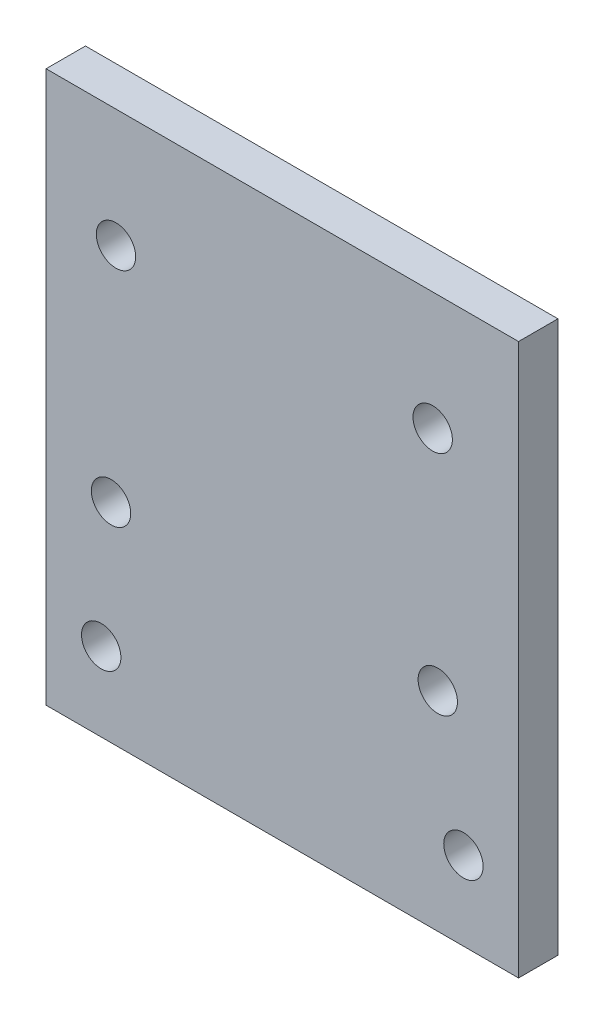
SolidWorks part; units mm, degrees
ref_plane "Front Plane" through (0, 0, 0) normal (0, 0, 1) x (1, 0, 0)
ref_plane "Top Plane" through (0, 0, 0) normal (0, 1, 0) x (1, 0, 0)
ref_plane "Right Plane" through (0, 0, 0) normal (1, 0, 0) x (0, 0, -1)
sketch "Sketch1" plane through (0, 0, 0) normal (0, 0, 1) x (1, 0, 0)
  line L0 (30, -70) -> (30, -83.0444) construction
  line L1 (0, 0) -> (60, 0)
  line L2 (0, 0) -> (0, -70)
  line L3 (0, -70) -> (60, -70)
  line L4 (60, 0) -> (60, -70)
  circle A0 centre (8.8797, -15) radius 2.5
  circle A1 centre (49.0964, -15) radius 2.5
  circle A2 centre (49.7432, -43.54) radius 2.5
  circle A3 centre (8.2522, -43.54) radius 2.5
  circle A4 centre (7, -60) radius 2.5
  circle A5 centre (53, -60) radius 2.5
  dimension "D3" = 5
  dimension "D1" = 60
  dimension "D2" = 70
  dimension "D4" = 7
  dimension "D5" = 10
extrude "Boss-Extrude1" add sketch "Sketch1" along normal blind 5
